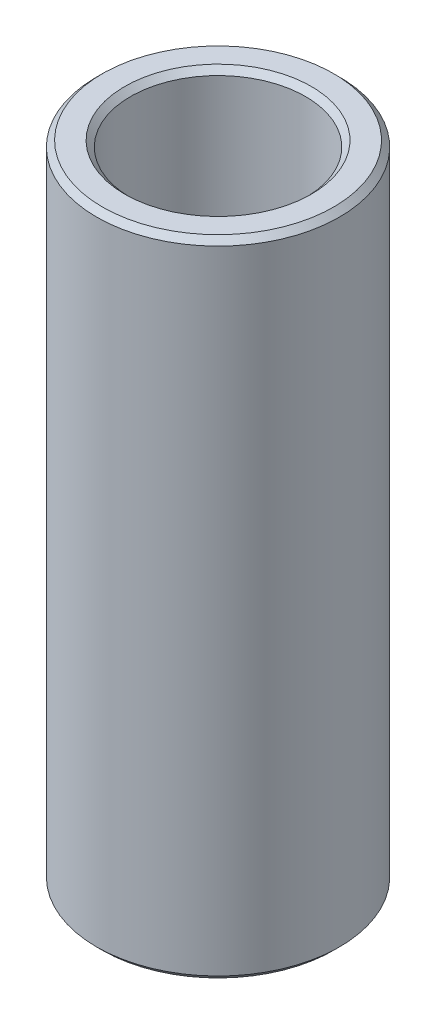
SolidWorks part; units mm, degrees
ref_plane "Front Plane" through (0, 0, 0) normal (0, 0, 1) x (1, 0, 0)
ref_plane "Top Plane" through (0, 0, 0) normal (0, 1, 0) x (1, 0, 0)
ref_plane "Right Plane" through (0, 0, 0) normal (1, 0, 0) x (0, 0, -1)
sketch "Sketch1" plane through (0, 0, 0) normal (0, 1, 0) x (1, 0, 0)
  circle A0 centre (0, 0) radius 42.5
  dimension "SLEEVE_OD" = 85
extrude "Boss-Extrude1" add sketch "Sketch1" along normal blind 225.3445
sketch "Sketch2" plane through (0, 0, 0) normal (0, 1, 0) x (1, 0, 0)
  circle A0 centre (0, 0) radius 30.6426
  dimension "BORE_D" = 61.2852
extrude "Cut-Extrude1" cut sketch "Sketch2" along normal through all
chamfer "Chamfer1" distance 2.0318 angle 45 4 edges at (0, 225.3445, 30.6426) (0, 0, 30.6426) (0, 0, 42.5) (0, 225.3445, 42.5)
